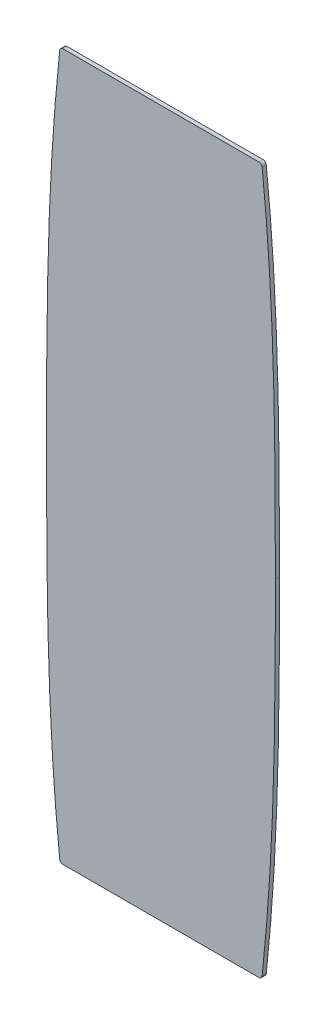
SolidWorks part; units mm, degrees
ref_plane "Front" through (0, 0, 0) normal (0, 0, 1) x (1, 0, 0)
ref_plane "Top" through (0, 0, 0) normal (0, 1, 0) x (1, 0, 0)
ref_plane "Right" through (0, 0, 0) normal (1, 0, 0) x (0, 0, -1)
sketch "Sketch1" plane through (0, 0, 0) normal (0, 0, 1) x (1, 0, 0)
  line L4 (-23.7959, -85.8) -> (23.7959, -85.8)
  line L5 (23.7959, 85.8) -> (-23.7959, 85.8)
  line L6 (-23.7959, -85.8) -> (23.7959, -85.8)
  line L7 (23.7959, 85.8) -> (-23.7959, 85.8)
  arc A8 (-24.5914, -85.0845) -> (-23.7959, -85.8) centre (-23.7959, -85) ccw
  arc A9 (23.7959, -85.8) -> (24.5914, -85.0845) centre (23.7959, -85) ccw
  arc A10 (24.5914, 85.0845) -> (23.7959, 85.8) centre (23.7959, 85) ccw
  arc A11 (-23.7959, 85.8) -> (-24.5914, 85.0845) centre (-23.7959, 85) ccw
  arc A12 (-24.5914, -85.0845) -> (-23.7959, -85.8) centre (-23.7959, -85) ccw
  arc A13 (23.7959, -85.8) -> (24.5914, -85.0845) centre (23.7959, -85) ccw
  arc A14 (24.5914, 85.0845) -> (23.7959, 85.8) centre (23.7959, 85) ccw
  arc A15 (-23.7959, 85.8) -> (-24.5914, 85.0845) centre (-23.7959, 85) ccw
  spline S8 degree 3 poles (-1813.6816, 775.3598) (38.2333, 514.2293) (-30.0727, 246.34) (-27.6629, -28.4006) (-27.5516, -35.4997) (-27.1348, -49.6946) (-26.8273, -56.7856) (-26.1559, -67.4085) (-25.8975, -70.9473) (6.4902, -456.0387) (490.043, -808.3332) (1630.7339, -1118.0367) knots -9.173904 -9.173904 -9.173904 -9.173904 0.25 0.25 0.5 0.5 0.75 0.75 0.875 0.875 14.362474 14.362474 14.362474 14.362474 only from (-27.8, 0) to (-24.5914, -85.0845)
  spline S9 degree 3 poles (-1805.145, -773.4019) (-243.2141, -617.0736) (8.2656, -350.3027) (26.8287, -56.7783) (27.1351, -49.686) (27.5518, -35.4924) (27.663, -28.3946) (30.0742, 246.5954) (-38.347, 515.2438) (1818.5454, 763.3075) knots -9.855908 -9.855908 -9.855908 -9.855908 0.25 0.25 0.5 0.5 0.75 0.75 10.184999 10.184999 10.184999 10.184999 only from (24.5914, -85.0845) to (27.8, 0)
  spline S10 degree 3 poles (1813.6816, -775.3598) (-38.2333, -514.2293) (30.0727, -246.34) (27.6629, 28.4006) (27.5516, 35.4997) (27.1348, 49.6946) (26.8273, 56.7856) (26.1559, 67.4085) (25.8975, 70.9473) (-6.4902, 456.0387) (-490.043, 808.3332) (-1630.7339, 1118.0367) knots -9.173904 -9.173904 -9.173904 -9.173904 0.25 0.25 0.5 0.5 0.75 0.75 0.875 0.875 14.362474 14.362474 14.362474 14.362474 only from (27.8, 0) to (24.5914, 85.0845)
  spline S11 degree 3 poles (1805.145, 773.4019) (243.2141, 617.0736) (-8.2656, 350.3027) (-26.8287, 56.7783) (-27.1351, 49.686) (-27.5518, 35.4924) (-27.663, 28.3946) (-30.0742, -246.5954) (38.347, -515.2438) (-1818.5454, -763.3075) knots -9.855908 -9.855908 -9.855908 -9.855908 0.25 0.25 0.5 0.5 0.75 0.75 10.184999 10.184999 10.184999 10.184999 only from (-24.5914, 85.0845) to (-27.8, 0)
  spline S12 degree 3 poles (-27.8, 0) (-27.8, -7.1003) (-27.7874, -14.2005) (-27.6629, -28.4006) (-27.5516, -35.4997) (-27.1348, -49.6946) (-26.8273, -56.7856) (-26.1559, -67.4085) (-25.8975, -70.9473) (-25.3027, -78.0197) (-24.9665, -81.5533) (-24.5914, -85.0845) knots 0 0 0 0 0.25 0.25 0.5 0.5 0.75 0.75 0.875 0.875 1 1 1 1
  spline S13 degree 3 poles (24.5914, -85.0845) (25.3415, -78.024) (25.9324, -70.9502) (26.8287, -56.7783) (27.1351, -49.686) (27.5518, -35.4924) (27.663, -28.3946) (27.7874, -14.1979) (27.8, -7.099) (27.8, 0) knots 0 0 0 0 0.25 0.25 0.5 0.5 0.75 0.75 1 1 1 1
  spline S14 degree 3 poles (27.8, 0) (27.8, 7.1003) (27.7874, 14.2005) (27.6629, 28.4006) (27.5516, 35.4997) (27.1348, 49.6946) (26.8273, 56.7856) (26.1559, 67.4085) (25.8975, 70.9473) (25.3027, 78.0197) (24.9665, 81.5533) (24.5914, 85.0845) knots 0 0 0 0 0.25 0.25 0.5 0.5 0.75 0.75 0.875 0.875 1 1 1 1
  spline S15 degree 3 poles (-24.5914, 85.0845) (-25.3415, 78.024) (-25.9324, 70.9502) (-26.8287, 56.7783) (-27.1351, 49.686) (-27.5518, 35.4924) (-27.663, 28.3946) (-27.7874, 14.1979) (-27.8, 7.099) (-27.8, 0) knots 0 0 0 0 0.25 0.25 0.5 0.5 0.75 0.75 1 1 1 1
  dimension "D1" = 0.2
extrude "Boss-Extrude1" add sketch "Sketch1" along normal up to surface (1 mm away)
